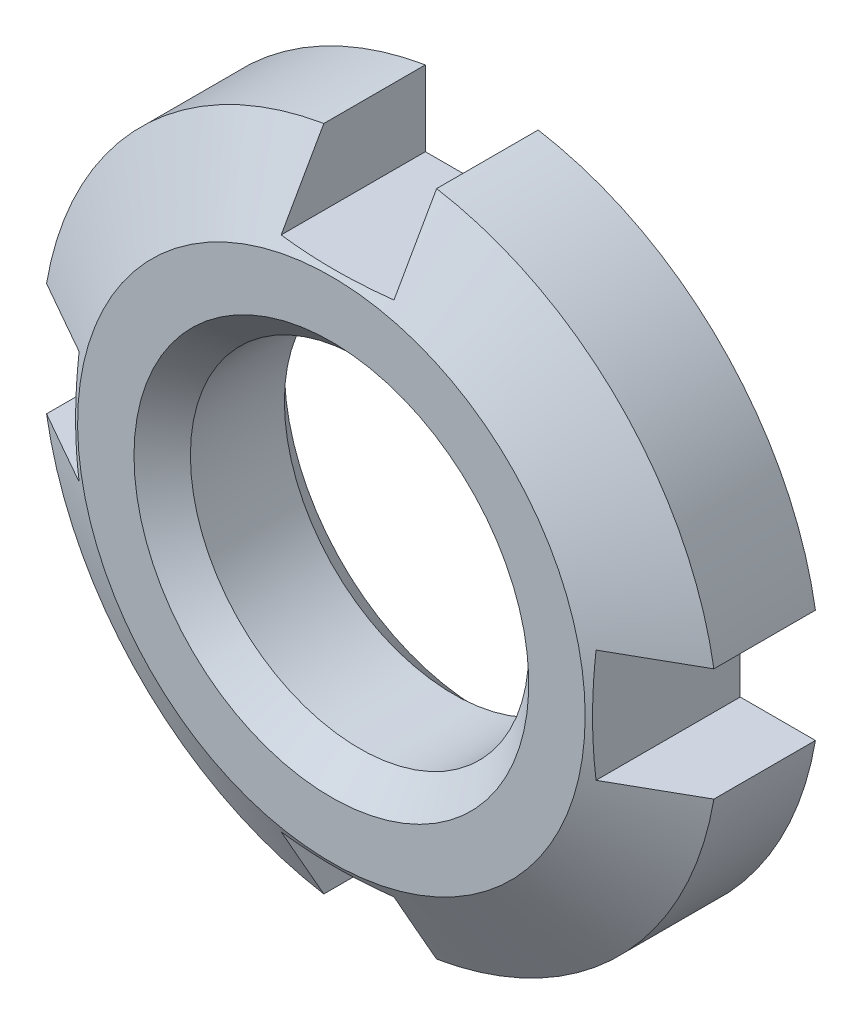
SolidWorks part; units mm, degrees
ref_plane "Front Plane" through (0, 0, 0) normal (0, 0, 1) x (1, 0, 0)
ref_plane "Top Plane" through (0, 0, 0) normal (0, 1, 0) x (1, 0, 0)
ref_plane "Right Plane" through (0, 0, 0) normal (1, 0, 0) x (0, 0, -1)
sketch "BaseNutSke" plane through (0, 0, 0) normal (0, 1, 0) x (1, 0, 0)
  line L0 (0, 0) -> (0, 9.527) construction
  line L1 (-6.75, -4) -> (0, -4)
  line L2 (-9, -2.701) -> (-9, 0)
  line L3 (-9, 0) -> (0, 0)
  line L4 (0, -4) -> (0, 0)
  line L5 (-6.75, -4) -> (-9, -2.701)
revolve "BaseNut" add sketch "BaseNutSke" angle 360 about L0
sketch "SlotSke" plane through (0, 0, 0) normal (0, 0, 1) x (1, 0, 0)
  line L0 (0, 0) -> (0, 19.9956) construction
  line L1 (-1.5, 9.8741) -> (1.5, 9.8741)
  line L2 (-1.5, 9.8741) -> (-1.5, 6.8741)
  line L3 (-1.5, 6.8741) -> (1.5, 6.8741)
  line L4 (1.5, 9.8741) -> (1.5, 6.8741)
  circle A0 centre (0, 0) radius 9 construction
  circle A1 centre (0, 0) radius 9 construction
  point P9 (1.5, 8.8741)
  dimension "Slot_width" = 3
  dimension "Slot_depth" = 2
extrude "CutSlot" cut sketch "SlotSke" along normal through all
pattern_circular "SlotPat" count 4 over 360 about axis through (0, 0, 0) along (0, 0, -1) of "CutSlot"
sketch "HoleSke" plane through (0, 0, 0) normal (0, 0, 1) x (1, 0, 0)
  circle A0 centre (0, 0) radius 4.5
extrude "TappedHole" cut sketch "HoleSke" along normal through all
cosmetic thread "ThreadCosmetic" [suppressed] parameters "Thread_major"=10
chamfer "Chamfer1" distance 0.75 angle 45 2 edges at (4.5, 0, 0) (4.5, 0, 4)
sketch "ThdSchSke" plane through (0, 0, 0) normal (0, 1, 0) x (1, 0, 0)
  line L0 (-5, -2.9613) -> (-4.5, -3.25)
  line L1 (-4.5, -3.25) -> (-3.9226, -3.25)
  line L2 (-3.9226, -3.25) -> (-3.9226, -2.6726)
  line L3 (-3.9226, -2.6726) -> (-4.5, -2.6726)
  line L4 (-4.5, -2.6726) -> (-5, -2.9613)
  line L5 (0, 0) -> (0, -27.9917) construction
  line L6 (-4.5, -3.25) -> (4.5, -3.25) construction
  dimension "D1" = 9
  dimension "D2" = 10
revolve "ThreadSchematic" [suppressed] cut sketch "ThdSchSke" angle 360 about L5
pattern_linear "ThdSchPat" [suppressed] count 4 along (0, 0, -1) of bodies 112
equation "\"D1@ThdSchSke\" = \"Tap_drill@HoleSke\""
equation "\"D2@ThdSchSke\" = \"Thread_major@ThreadCosmetic\""
equation "\"ADVANCE@ThdSchPat\" = \"ADVANCE@Chamfer1\""
equation "\"D1@ThdSchPat\" =  int(  ( \"Thickness@BaseNutSke\"  - 2 *  \"ADVANCE@Chamfer1\" ) / \"ADVANCE@Chamfer1\" )  + 1"
